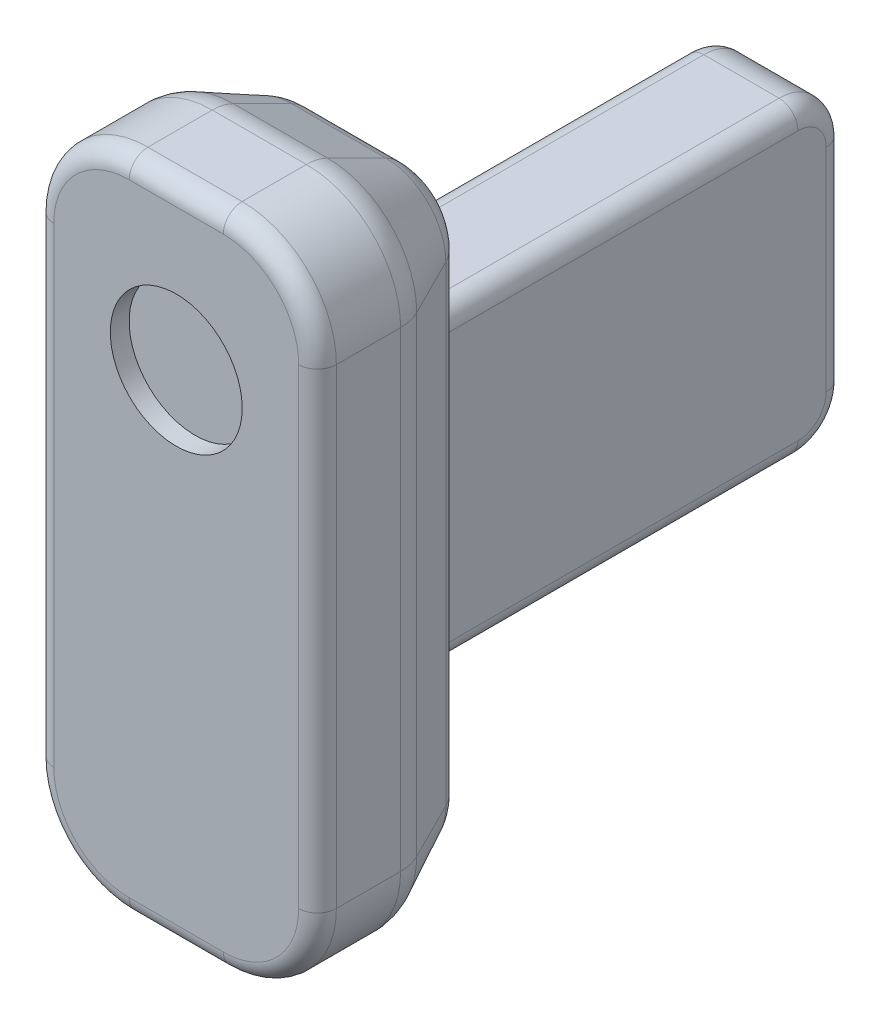
SolidWorks part; units mm, degrees
ref_plane "Front Plane" through (0, 0, 0) normal (0, 0, 1) x (1, 0, 0)
ref_plane "Top Plane" through (0, 0, 0) normal (0, 1, 0) x (1, 0, 0)
ref_plane "Right Plane" through (0, 0, 0) normal (1, 0, 0) x (0, 0, -1)
sketch "Sketch1" plane through (0, 0, 0) normal (0, 0, 1) x (1, 0, 0)
  line L1 (42.3673, -46.3138) -> (72.3673, -46.3138)
  line L2 (42.3673, -46.3138) -> (42.3673, -116.3138)
  line L3 (42.3673, -116.3138) -> (72.3673, -116.3138)
  line L4 (72.3673, -46.3138) -> (72.3673, -116.3138)
  dimension "D1" = 30
  dimension "D2" = 70
extrude "Boss-Extrude1" add sketch "Sketch1" against normal blind 20
fillet "Fillet1" radius 10 4 edges at (42.3673, -46.3138, -10) (72.3673, -46.3138, -10) (42.3673, -116.3138, -10) (72.3673, -116.3138, -10)
fillet "Fillet2" radius 2 8 edges at (69.4383, -113.3848, 0) (57.3673, -116.3138, 0) (45.2962, -113.3848, 0) (42.3673, -81.3138, 0) (45.2962, -49.2427, 0) (57.3673, -46.3138, 0) (69.4383, -49.2427, 0) (72.3673, -81.3138, 0)
chamfer "Chamfer1" distance 5 distance2 10 8 edges at (42.3673, -81.3138, -20) (45.2962, -113.3848, -20) (45.2962, -49.2427, -20) (57.3673, -116.3138, -20) (57.3673, -46.3138, -20) (69.4383, -113.3848, -20) (69.4383, -49.2427, -20) (72.3673, -81.3138, -20) first distance on face at (57.3673, -81.3138, -20)
fillet "Fillet3" radius 5 16 edges at (65.9028, -52.7782, -20) (57.3673, -51.3138, -20) (48.8317, -52.7782, -20) (47.3673, -81.3138, -20) (48.8317, -109.8493, -20) (57.3673, -111.3138, -20) (65.9028, -109.8493, -20) (69.4383, -113.3848, -10) (57.3673, -116.3138, -10) (45.2962, -113.3848, -10) (42.3673, -81.3138, -10) (45.2962, -49.2427, -10) (57.3673, -46.3138, -10) (69.4383, -49.2427, -10) (67.3673, -81.3138, -20) (72.3673, -81.3138, -10)
sketch "Sketch2" plane through (0, 0, -20) normal (0, 0, -1) x (-1, 0, 0)
  line L0 (-64.2771, -81.3138) -> (-50.4574, -81.3138) construction
  line L1 (-64.2771, -56.3138) -> (-64.2771, -106.3138) construction
  line L2 (-50.4574, -106.3138) -> (-50.4574, -56.3138) construction
  line L3 (-57.3673, -108.2236) -> (-57.3673, -54.4039) construction
  line L4 (-62.3673, -108.2236) -> (-52.3673, -108.2236) construction
  line L5 (-52.3673, -54.4039) -> (-62.3673, -54.4039) construction
  line L7 (-63.3673, -98.8138) -> (-51.3673, -98.8138)
  line L8 (-63.3673, -98.8138) -> (-63.3673, -66.3138)
  line L9 (-63.3673, -66.3138) -> (-51.3673, -66.3138)
  line L10 (-51.3673, -98.8138) -> (-51.3673, -66.3138)
  dimension "D3" = 32.5
extrude "Boss-Extrude2" add sketch "Sketch2" along normal blind 45
fillet "Fillet4" radius 5 2 edges at (57.3673, -66.3138, -65) (57.3673, -98.8138, -65)
sketch "Sketch3" plane through (0, 0, 0) normal (0, 0, 1) x (1, 0, 0)
  line L0 (57.3673, -48.3138) -> (57.3673, -114.3138) construction
  line L1 (62.3673, -48.3138) -> (52.3673, -48.3138) construction
  line L2 (52.3673, -114.3138) -> (62.3673, -114.3138) construction
  line L3 (52.3673, -46.3138) -> (62.3673, -46.3138) construction
  circle A0 centre (57.3673, -63.3138) radius 7
  dimension "D1" = 17
extrude "Cut-Extrude1" cut sketch "Sketch3" against normal blind 2
fillet "Fillet5" radius 2 10 edges at (51.3673, -66.3138, -40) (51.3673, -67.7782, -63.5355) (51.3673, -82.5638, -65) (51.3673, -97.3493, -63.5355) (63.3673, -66.3138, -40) (63.3673, -67.7782, -63.5355) (63.3673, -82.5638, -65) (63.3673, -97.3493, -63.5355) (51.3673, -98.8138, -40) (63.3673, -98.8138, -40)
